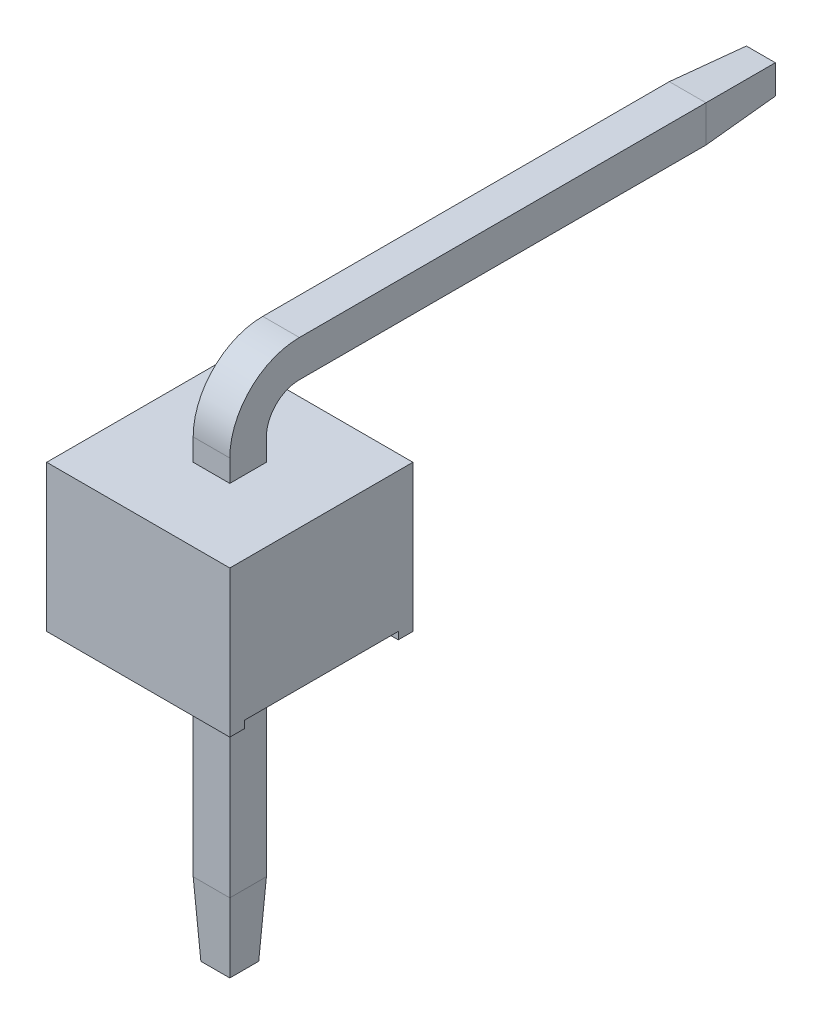
SolidWorks part; units mm, degrees
ref_plane "Alzado" through (0, 0, 0) normal (0, 0, 1) x (1, 0, 0)
ref_plane "Planta" through (0, 0, 0) normal (0, 1, 0) x (1, 0, 0)
ref_plane "Vista lateral" through (0, 0, 0) normal (1, 0, 0) x (0, 0, -1)
sketch "Croquis1" plane through (0, 0, 0) normal (0, 1, 0) x (1, 0, 0)
  line L1 (-1.25, -1.25) -> (1.25, -1.25)
  line L2 (-1.25, -1.25) -> (-1.25, 1.25)
  line L3 (-1.25, 1.25) -> (1.25, 1.25)
  line L4 (1.25, -1.25) -> (1.25, 1.25)
  line L5 (-1.25, -1.25) -> (1.25, 1.25) construction
  line L6 (-1.25, 1.25) -> (1.25, -1.25) construction
  point P0 (0, 0)
  dimension "D1" = 2.5
extrude "Saliente-Extruir1" add sketch "Croquis1" along normal blind 2
sketch "Croquis2" plane through (0, 0, 0) normal (0, -1, 0) x (1, 0, 0)
  line L0 (1.25, 1.25) -> (1.25, -1.25) construction
  line L1 (-1.25, -1.05) -> (1.25, -1.05)
  line L2 (-1.25, -1.05) -> (-1.25, 1.05)
  line L3 (-1.25, 1.05) -> (1.25, 1.05)
  line L4 (1.25, -1.05) -> (1.25, 1.05)
  line L5 (-1.25, -1.05) -> (1.25, 1.05) construction
  line L6 (-1.25, 1.05) -> (1.25, -1.05) construction
  line L7 (-1.25, 1.25) -> (1.25, 1.25) construction
  point P0 (0, 0)
  dimension "D1" = 0.2
extrude "Cortar-Extruir1" cut sketch "Croquis2" against normal blind 0.1
sketch "Croquis3" plane through (0, 0.1, 0) normal (0, -1, 0) x (1, 0, 0)
  line L1 (-0.25, -0.25) -> (0.25, -0.25)
  line L2 (-0.25, -0.25) -> (-0.25, 0.25)
  line L3 (-0.25, 0.25) -> (0.25, 0.25)
  line L4 (0.25, -0.25) -> (0.25, 0.25)
  line L5 (-0.25, -0.25) -> (0.25, 0.25) construction
  line L6 (-0.25, 0.25) -> (0.25, -0.25) construction
  point P0 (0, 0)
  dimension "D1" = 0.5
extrude "Saliente-Extruir2" add sketch "Croquis3" along normal blind 4
ref_plane "Plano1" through (0, -2.9, 0) normal (0, -1, 0) x (-1, 0, 0)
sketch "Croquis5" plane through (0, -2.9, 0) normal (0, -1, 0) x (-1, 0, 0)
  line L4 (-0.25, 0.25) -> (-0.25, -0.25)
  line L5 (-0.25, -0.25) -> (0.25, -0.25)
  line L6 (0.25, -0.25) -> (0.25, 0.25)
  line L7 (0.25, 0.25) -> (-0.25, 0.25)
  line L8 (-0.25, 0.25) -> (-0.25, -0.25)
  line L9 (-0.25, -0.25) -> (0.25, -0.25)
  line L10 (0.25, -0.25) -> (0.25, 0.25)
  line L11 (0.25, 0.25) -> (-0.25, 0.25)
  dimension "D1" = 0
extrude "Cortar-Extruir2" cut sketch "Croquis5" along normal blind 1 draft 3 flip side to cut draft outward yes
sketch "Croquis6" plane through (0, 2, 0) normal (0, 1, 0) x (1, 0, 0)
  line L0 (-0.25, 0.25) -> (0.25, 0.25) construction
  line L1 (-0.25, -0.25) -> (-0.25, 0.25) construction
  line L2 (0.25, 0.25) -> (0.25, -0.25) construction
  line L3 (0.25, -0.25) -> (-0.25, -0.25) construction
  line L4 (-0.25, 0.25) -> (0.25, 0.25)
  line L5 (-0.25, -0.25) -> (-0.25, 0.25)
  line L6 (0.25, 0.25) -> (0.25, -0.25)
  line L7 (0.25, -0.25) -> (-0.25, -0.25)
ref_plane "Plano2" through (0, 0, 0) normal (1, 0, 0) x (0, 0, -1)
sketch "Croquis7" plane through (0, 0, 0) normal (1, 0, 0) x (0, 0, -1)
  line L0 (0, 2) -> (0, 2.3)
  line L1 (-0.25, 2) -> (0.25, 2) construction
  line L2 (0.7, 3) -> (7.25, 3)
  line L3 (1.25, 2) -> (1.25, 0) construction
  arc A0 (0.7, 3) -> (0, 2.3) centre (0.7, 2.3) ccw
  dimension "D2" = 0.7
  dimension "D1" = 6
sweep "Barrer1" add profiles "Croquis6" path "Croquis7"
ref_plane "Plano3" through (0, 0, -6.25) normal (0, 0, -1) x (-1, 0, 0)
sketch "Croquis8" plane through (0, 0, -6.25) normal (0, 0, -1) x (-1, 0, 0)
  line L4 (0.25, 2.75) -> (0.25, 3.25)
  line L5 (0.25, 3.25) -> (-0.25, 3.25)
  line L6 (-0.25, 3.25) -> (-0.25, 2.75)
  line L7 (-0.25, 2.75) -> (0.25, 2.75)
  line L8 (0.25, 2.75) -> (0.25, 3.25)
  line L9 (0.25, 3.25) -> (-0.25, 3.25)
  line L10 (-0.25, 3.25) -> (-0.25, 2.75)
  line L11 (-0.25, 2.75) -> (0.25, 2.75)
  dimension "D1" = 0
extrude "Cortar-Extruir3" cut sketch "Croquis8" along normal blind 1 draft 3 flip side to cut draft outward yes
